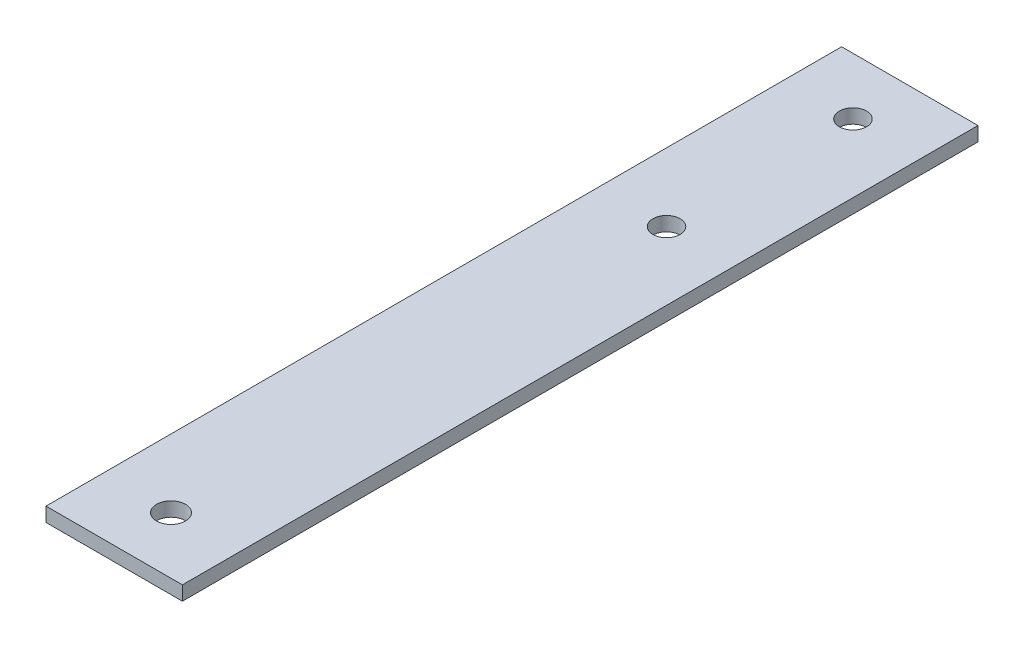
SolidWorks part; units mm, degrees
ref_plane "Front Plane" through (0, 0, 0) normal (0, 0, 1) x (1, 0, 0)
ref_plane "Top Plane" through (0, 0, 0) normal (0, 1, 0) x (1, 0, 0)
ref_plane "Right Plane" through (0, 0, 0) normal (1, 0, 0) x (0, 0, -1)
sketch "Sketch1" plane through (0, 0, 0) normal (0, 1, 0) x (1, 0, 0)
  line L0 (-20.7239, 88.9) -> (-20.7239, -88.9)
  line L1 (-51.2039, 88.9) -> (-20.7239, 88.9)
  line L2 (-51.2039, -88.9) -> (-20.7239, -88.9)
  line L3 (-51.2039, 88.9) -> (-51.2039, -88.9)
  circle A0 centre (-35.9639, 76.2) radius 3.048
  circle A1 centre (-35.9639, 34.5293) radius 3.048
  circle A2 centre (-35.9639, -76.2) radius 3.2385
  point P1 (-35.9639, 88.9)
  point P5 (-20.7239, 0)
  dimension "D1" = 6.096
  dimension "D4" = 6.477
  dimension "D2" = 12.7
  dimension "D3" = 41.6707
extrude "Boss-Extrude1" add sketch "Sketch1" along normal blind 3.175
